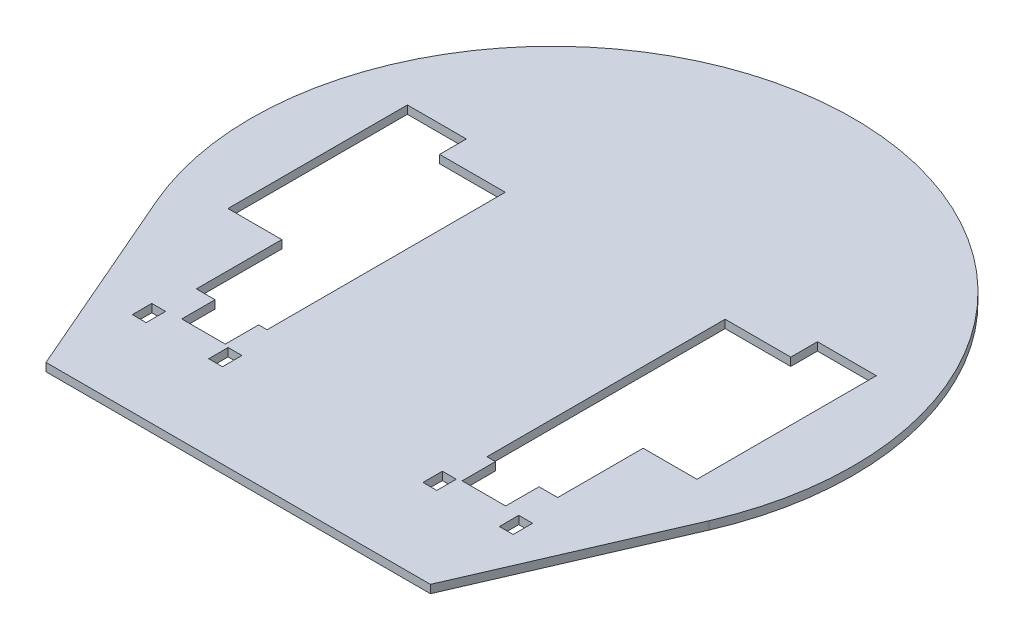
SolidWorks part; units mm, degrees
ref_plane "Front Plane" through (0, 0, 0) normal (0, 0, 1) x (1, 0, 0)
ref_plane "Top Plane" through (0, 0, 0) normal (0, 1, 0) x (1, 0, 0)
ref_plane "Right Plane" through (0, 0, 0) normal (1, 0, 0) x (0, 0, -1)
sketch "Sketch1" plane through (0, 0, 0) normal (0, 1, 0) x (1, 0, 0)
  circle A0 centre (0, 0) radius 117.5
  dimension "D1" = 235
extrude "Boss-Extrude1" add sketch "Sketch1" along normal blind 3.175
sketch "Sketch3" plane through (0, 0, 0) normal (0, 1, 0) x (1, 0, 0)
  line L3 (-107.8261, -46.6881) -> (-75, -122.5)
  line L5 (-75, -122.5) -> (75, -122.5)
  line L6 (75, -122.5) -> (107.8261, -46.6881)
  line L7 (107.8261, -46.6881) -> (-107.8261, -46.6881)
  line L8 (0, -122.5) -> (0, -117.5) construction
  circle A2 centre (0, 0) radius 117.5 construction
  dimension "D1" = 150
  dimension "D2" = 5
extrude "Boss-Extrude2" add sketch "Sketch3" along normal up to surface (3.175 mm away) up to face at (0, 3.175, 117.5)
sketch "Sketch4" plane through (0, 3.175, 0) normal (0, 1, 0) x (1, 0, 0)
  line L0 (-70, -30) -> (-70, 30) construction
  line L1 (-90, 30) -> (-90, -30) construction
  line L2 (-70, -30) -> (-70, 30) construction
  line L3 (-90, 30) -> (-90, -30) construction
  line L4 (-91.5, 35) -> (-68.5, 35)
  line L5 (-69, 19.5885) -> (-69, -54.8563) construction
  line L6 (-68.5, 35) -> (-68.5, 24.5885)
  line L7 (-44.4, 19.5885) -> (-44.4, -54.8563) construction
  line L8 (-68.5, 24.5885) -> (-42.9, 24.5885)
  line L9 (-42.9, 24.5885) -> (-42.9, -68.3372)
  line L10 (-42.9, -68.3372) -> (-70.5, -68.3372)
  line L11 (-70.5, -68.3372) -> (-70.5, -35)
  line L12 (-70.5, -35) -> (-91.5, -35)
  line L13 (-91.5, -35) -> (-91.5, 35)
  line L14 (-90, -30) -> (-90, -35) construction
  line L15 (-44.4, 24.5885) -> (-44.4, 19.5885) construction
  line L16 (-44.4, 19.5885) -> (-42.9, 19.5885) construction
  line L17 (-42.9, -54.8563) -> (-44.4, -54.8563) construction
  line L18 (-44.4, -54.8563) -> (-44.4, -68.3372) construction
  line L19 (-69, -68.3372) -> (-69, -54.8563) construction
  line L20 (-69, -54.8563) -> (-70.5, -54.8563) construction
  line L21 (-90, 35) -> (-90, 30) construction
  line L22 (-90, 30) -> (-91.5, 30) construction
  line L23 (-70, 35) -> (-70, 30) construction
  line L24 (-70, 30) -> (-68.5, 30) construction
  line L25 (0, 0) -> (0, 30.6953) construction
  line L26 (91.5, -35) -> (91.5, 35)
  line L27 (70.5, -35) -> (91.5, -35)
  line L28 (70.5, -68.3372) -> (70.5, -35)
  line L29 (42.9, -68.3372) -> (70.5, -68.3372)
  line L30 (42.9, 24.5885) -> (42.9, -68.3372)
  line L31 (68.5, 24.5885) -> (42.9, 24.5885)
  line L32 (68.5, 35) -> (68.5, 24.5885)
  line L33 (91.5, 35) -> (68.5, 35)
  line L34 (-68.9093, -68.3372) -> (-44.4907, -68.3372) construction
  dimension "D1" = 1.5
  dimension "D2" = 5
extrude "Cut-Extrude1" cut sketch "Sketch4" against normal through all
sketch "Sketch6" plane through (0, 0, 0) normal (0, -1, 0) x (1, 0, 0)
  line L0 (-70.5, 68.3372) -> (-42.9, 68.3372) construction
  line L1 (-63.2, 68.3372) -> (-46.2, 68.3372)
  line L2 (-63.2, 68.3372) -> (-63.2, 81.3372)
  line L3 (-63.2, 81.3372) -> (-46.2, 81.3372)
  line L4 (-46.2, 68.3372) -> (-46.2, 81.3372)
  line L5 (-39.3, 82.1344) -> (-39.3, 89.3188) construction
  line L6 (-39.3, 89.3188) -> (-44.3, 89.3188) construction
  line L7 (-44.3, 89.3188) -> (-44.3, 82.1344) construction
  line L8 (-44.3, 82.1344) -> (-39.3, 82.1344) construction
  line L9 (-74.1, 89.3188) -> (-74.1, 82.1344) construction
  line L10 (-74.1, 82.1344) -> (-69.1, 82.1344) construction
  line L11 (-69.1, 82.1344) -> (-69.1, 89.3188) construction
  line L12 (-69.1, 89.3188) -> (-74.1, 89.3188) construction
  line L13 (-39.3, 82.1344) -> (-39.3, 89.3188) construction
  line L14 (-39.3, 89.3188) -> (-44.3, 89.3188) construction
  line L15 (-44.3, 89.3188) -> (-44.3, 82.1344) construction
  line L16 (-44.3, 82.1344) -> (-39.3, 82.1344) construction
  line L17 (-74.1, 89.3188) -> (-74.1, 82.1344) construction
  line L18 (-74.1, 82.1344) -> (-69.1, 82.1344) construction
  line L19 (-69.1, 82.1344) -> (-69.1, 89.3188) construction
  line L20 (-69.1, 89.3188) -> (-74.1, 89.3188) construction
  line L21 (-74.3, 89.5188) -> (-74.3, 81.9344)
  line L22 (-74.3, 81.9344) -> (-68.9, 81.9344)
  line L23 (-68.9, 81.9344) -> (-68.9, 89.5188)
  line L24 (-68.9, 89.5188) -> (-74.3, 89.5188)
  line L25 (-39.1, 81.9344) -> (-39.1, 89.5188)
  line L26 (-39.1, 89.5188) -> (-44.5, 89.5188)
  line L27 (-44.5, 89.5188) -> (-44.5, 81.9344)
  line L28 (-44.5, 81.9344) -> (-39.1, 81.9344)
  line L29 (-61.7, 74.3188) -> (-47.7, 74.3188) construction
  line L30 (-47.7, 71.1688) -> (-47.7, 77.4688) construction
  line L31 (-54.7, 74.3188) -> (-54.7, 81.3372) construction
  line L32 (0, 0) -> (0, 39.0571) construction
  line L33 (54.7, 74.3188) -> (54.7, 81.3372) construction
  line L34 (61.7, 74.3188) -> (47.7, 74.3188) construction
  line L35 (69.1, 89.3188) -> (74.1, 89.3188) construction
  line L36 (69.1, 82.1344) -> (69.1, 89.3188) construction
  line L37 (74.1, 82.1344) -> (69.1, 82.1344) construction
  line L38 (74.1, 89.3188) -> (74.1, 82.1344) construction
  line L39 (44.3, 82.1344) -> (39.3, 82.1344) construction
  line L40 (44.3, 89.3188) -> (44.3, 82.1344) construction
  line L41 (39.3, 89.3188) -> (44.3, 89.3188) construction
  line L42 (39.3, 82.1344) -> (39.3, 89.3188) construction
  line L43 (44.5, 81.9344) -> (39.1, 81.9344)
  line L44 (44.5, 89.5188) -> (44.5, 81.9344)
  line L45 (39.1, 89.5188) -> (44.5, 89.5188)
  line L46 (39.1, 81.9344) -> (39.1, 89.5188)
  line L47 (68.9, 89.5188) -> (74.3, 89.5188)
  line L48 (68.9, 81.9344) -> (68.9, 89.5188)
  line L49 (74.3, 81.9344) -> (68.9, 81.9344)
  line L50 (74.3, 89.5188) -> (74.3, 81.9344)
  line L51 (46.2, 68.3372) -> (46.2, 81.3372)
  line L52 (63.2, 81.3372) -> (46.2, 81.3372)
  line L53 (63.2, 68.3372) -> (63.2, 81.3372)
  line L54 (63.2, 68.3372) -> (46.2, 68.3372)
  point P22 (-54.7, 68.3372)
  point P57 (54.7, 68.3372)
  dimension "D2" = 13
  dimension "D3" = 17
  dimension "D1" = 0.2
extrude "Cut-Extrude2" cut sketch "Sketch6" against normal through all
